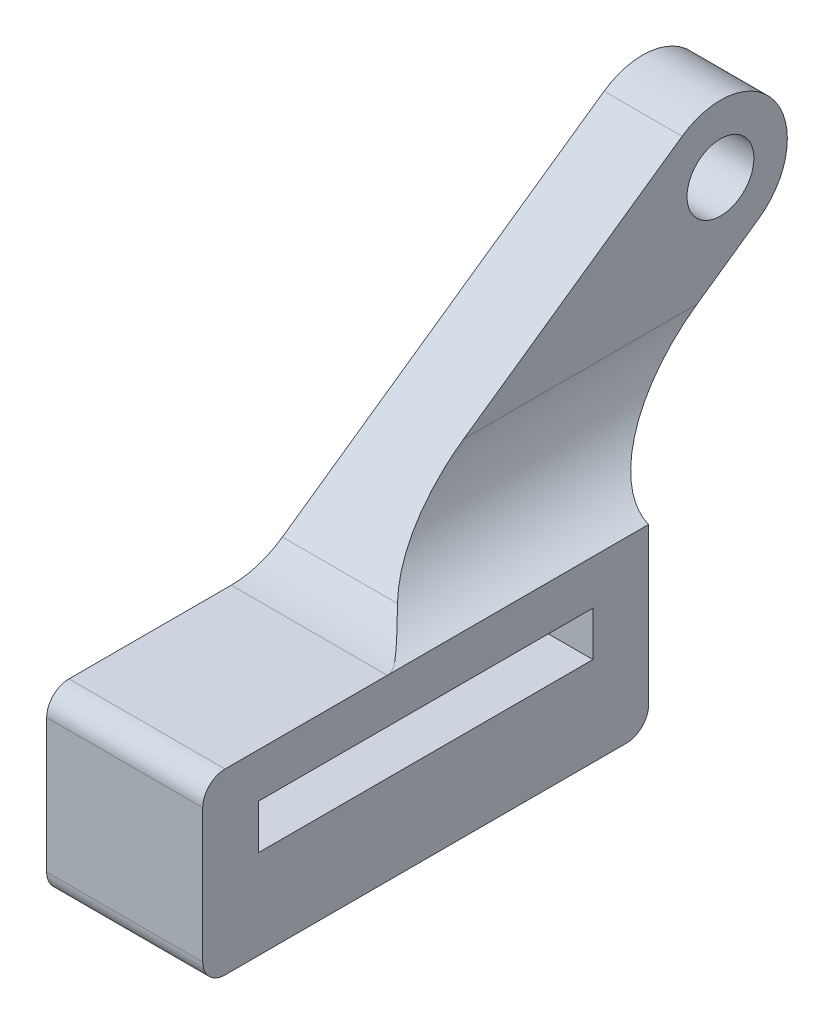
SolidWorks part; units mm, degrees
ref_plane "Alzado" through (0, 0, 0) normal (0, 0, 1) x (1, 0, 0)
ref_plane "Planta" through (0, 0, 0) normal (0, 1, 0) x (1, 0, 0)
ref_plane "Vista lateral" through (0, 0, 0) normal (1, 0, 0) x (0, 0, -1)
sketch "Croquis1" plane through (0, 0, 0) normal (1, 0, 0) x (0, 0, -1)
  line L0 (-0.4607, 4) -> (15, 14.8257)
  line L1 (10, -4) -> (-10, -4)
  line L2 (10, -4) -> (10, 4)
  line L3 (-0.4607, 4) -> (-10, 4)
  line L4 (-10, -4) -> (-10, 4)
  line L5 (10, -4) -> (-10, 4) construction
  line L6 (10, 4) -> (-10, -4) construction
  line L7 (7.5, 2) -> (-7.5, 2)
  line L8 (7.5, 2) -> (7.5, 0)
  line L9 (7.5, 0) -> (-7.5, 0)
  line L10 (-7.5, 2) -> (-7.5, 0)
  line L11 (7.5, 2) -> (-7.5, 0) construction
  line L12 (7.5, 0) -> (-7.5, 2) construction
  line L13 (10, 4) -> (18.4415, 9.9108)
  line L16 (-0.4607, 4) -> (10, 4) construction
  line L17 (15, 14.8257) -> (18.4415, 9.9108) construction
  arc A0 (18.4415, 9.9108) -> (15, 14.8257) centre (16.7207, 12.3682) ccw
  circle A1 centre (16.7207, 12.3682) radius 1.5
  point P0 (0, 0)
  point P6 (0, 1)
  dimension "D9" = 3
  dimension "D1" = 8
  dimension "D2" = 20
  dimension "D3" = 15
  dimension "D4" = 2
  dimension "D5" = 2
  dimension "D6" = 5
  dimension "D7" = 6
  dimension "D8" = 35
extrude "Saliente-Extruir1" add sketch "Croquis1" along normal mid plane 7
sketch "Croquis2" plane through (3.5, 0, 0) normal (1, 0, 0) x (0, 0, -1)
  line L0 (-0.4607, 4) -> (10, 4)
  line L6 (-10, 4) -> (-10, -4)
  line L7 (-10, -4) -> (10, -4)
  line L8 (10, -4) -> (10, 4)
  line L9 (10, 4) -> (18.4415, 9.9108)
  line L10 (15, 14.8257) -> (-0.4607, 4)
  line L11 (-0.4607, 4) -> (-10, 4)
  line L15 (10, 4) -> (18.4415, 9.9108)
  line L16 (15, 14.8257) -> (-0.4607, 4)
  arc A1 (18.4415, 9.9108) -> (15, 14.8257) centre (16.7207, 12.3682) ccw
  arc A2 (18.4415, 9.9108) -> (15, 14.8257) centre (16.7207, 12.3682) ccw
  dimension "D1" = 0
extrude "Cortar-Extruir1" cut sketch "Croquis2" against normal up to surface (3.5 mm away)
fillet "Redondeo2" radius 4 2 edges at (0, 4, -4.7697) (-1.75, 4, 0.4607)
fillet "Redondeo3" radius 1 3 edges at (0, 4, 10) (0, -4, -10) (0, -4, 10)
